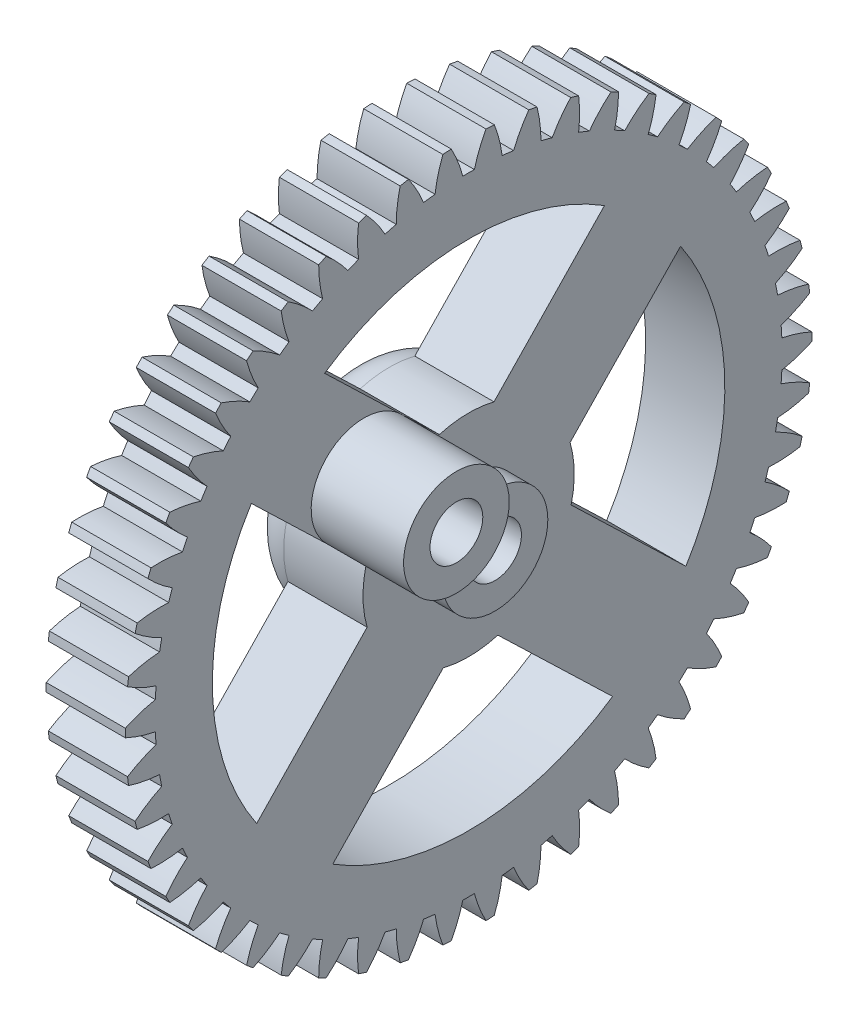
SolidWorks part; units mm, degrees
ref_plane "Plane1" through (0, 0, 0) normal (0, 0, 1) x (1, 0, 0)
ref_plane "Plane2" through (0, 0, 0) normal (0, 1, 0) x (1, 0, 0)
ref_plane "Plane3" through (0, 0, 0) normal (1, 0, 0) x (0, 0, -1)
other "Configuration Table"
sketch "HoldingSke" plane through (0, 0, 0) normal (0, 1, 0) x (1, 0, 0)
  line L0 (0, 0) -> (1.2856, -1.5321)
  line L1 (-15, 0) -> (100, 0) construction
  line L2 (0, 0) -> (-2.1039, 2.3779)
  line L3 (0, 0) -> (-11.863, 4.5341)
  line L4 (0, 0) -> (5.5511, 6.6156)
  line L5 (0, 0) -> (-46.8476, -17.4728)
  line L6 (0, 0) -> (-2.4869, -1.6779)
  line L7 (-2.1039, 2.3779) -> (8.6586, 51.2059)
  line L8 (-76.2, 54.61) -> (-75.9, 54.61)
  line L9 (-71.009, 38.7566) -> (-53.1078, 45.2721)
  line L10 (-76.2, 71.12) -> (104.1128, 71.12)
  line L11 (0, 0) -> (-3, 0)
  line L12 (-76.2, 101.6) -> (-76.181, 101.6)
  line L13 (24.9733, 27.94) -> (52.9518, 28.4284)
  line L14 (24.9733, 27.94) -> (24.9743, 27.94)
  line L15 (24.9733, 27.94) -> (100.4006, 29.5858)
  line L16 (-63.627, -0.5) -> (-12.827, -0.5)
  circle A0 centre (0, 0) radius 1
  circle A1 centre (0, 0) radius 11.874
  circle A2 centre (0, 0) radius 37.5
  circle A3 centre (0, 0) radius 1
  dimension "Num_teeth" = 50
  dimension "Pitch_radius" = 180.3128
  dimension "Width" = 3
  dimension "Thickness" = 3
sketch "BasProSke" plane through (0, 0, 0) normal (0, 1, 0) x (1, 0, 0)
  line L0 (-10, 0) -> (60, 0) construction
  line L1 (0, 0) -> (0, 13)
  line L2 (0, 0) -> (3, 0)
  line L3 (3, 0) -> (3, 13)
  line L4 (3, 13) -> (0, 13)
  dimension "Thickness" = 3
  dimension "Diameter" = 26
revolve "Base-Revolve" add sketch "BasProSke" angle 360 about L0
sketch "TooCutSke" plane through (0, 0, 0) normal (1, 0, 0) x (0, 0, -1)
  line L1 (0, 0) -> (0, 107) construction
  line L2 (0, 0) -> (-0.4259, 12.4927) construction
  line L3 (0, 0) -> (-1.5691, 24.9404) construction
  line L4 (-0.4259, 12.4927) -> (-0.7846, 12.4702) construction
  arc A0 (0.2187, 11.872) -> (-0.2187, 11.872) centre (0, 0) ccw
  arc A1 (0.6715, 13.0081) -> (-0.6715, 13.0081) centre (0, 0) ccw
  circle A2 centre (0, 0) radius 12.5 construction
  circle A3 centre (0, 0) radius 11.7462 construction
  arc A4 (-0.2187, 11.872) -> (-0.6715, 13.0081) centre (-5.0549, 10.6028) ccw
  arc A5 (0.6715, 13.0081) -> (0.2187, 11.872) centre (5.0549, 10.6028) ccw
extrude "ToothCut" cut sketch "TooCutSke" along normal through all
fillet "Breaks" [suppressed] radius 0.01 tangent propagation no
fillet "RootFillets" [suppressed] radius 0.126
pattern_circular "TeethCuts" count 50 every 7.2 about axis through (-10, 0, 0) along (1, 0, 0) of "ToothCut", "RootFillets", "Breaks"
sketch "HubNeaOneSke" plane through (0, 0, 0) normal (-1, 0, 0) x (0, 0, 1)
  circle A0 centre (0, 0) radius 11.874
  dimension "Diameter" = 23.748
extrude "HubNearOne" [suppressed] add sketch "HubNeaOneSke" along normal blind 47.0001
sketch "HubNeaBotSke" plane through (0, 0, 0) normal (-1, 0, 0) x (0, 0, 1)
  circle A0 centre (0, 0) radius 11.874
  dimension "Diameter" = 23.748
extrude "HubNearBoth" [suppressed] add sketch "HubNeaBotSke" along normal blind 23.5
ref_plane "FarPln" through (3, 0, 0) normal (1, 0, 0) x (0, 0, -1)
sketch "HubFarSke" plane through (3, 0, 0) normal (1, 0, 0) x (0, 0, -1)
  circle A0 centre (0, 0) radius 11.874
  dimension "Diameter" = 23.748
extrude "HubFar" [suppressed] add sketch "HubFarSke" along normal blind 23.5
sketch "BorSke" plane through (0, 0, 0) normal (1, 0, 0) x (0, 0, -1)
  circle A0 centre (0, 0) radius 1
  dimension "Diameter" = 2
extrude "Bore" cut sketch "BorSke" along normal mid plane 100.0001
sketch "KeySke" plane through (0, 0, 0) normal (1, 0, 0) x (0, 0, -1)
  line L0 (-0.4, 0) -> (-0.4, 1.3)
  line L1 (-0.4, 1.3) -> (0.4, 1.3)
  line L2 (0.4, 1.3) -> (0.4, 0)
  line L3 (0, 0) -> (0, 34) construction
  line L4 (-0.4, 0) -> (0.4, 0)
  dimension "Width" = 0.8
extrude "Keyway" [suppressed] cut sketch "KeySke" along normal mid plane 100.0001
pattern_circular "Keyway2" [suppressed] count 2 every 90 about axis through (-10, 0, 0) along (1, 0, 0)
sketch "草图1" plane through (3, 0, 0) normal (1, 0, 0) x (0, 0, -1)
  circle A0 centre (-3.9622, 3.8146) radius 1
  circle A1 centre (0, 0) radius 1 construction
  dimension "D1" = 5.5
extrude "切除-拉伸1" cut sketch "草图1" against normal blind 2
sketch "草图2" plane through (0, 0, 0) normal (-1, 0, 0) x (0, 0, 1)
  circle A0 centre (0, 0) radius 4
  circle A1 centre (0, 0) radius 1
extrude "凸台-拉伸1" add sketch "草图2" along normal blind 1.5
fillet "圆角1" radius 1.5 1 edges at (-1.5, 0, 4)
sketch "草图3" plane through (3, 0, 0) normal (1, 0, 0) x (0, 0, -1)
  circle A0 centre (-3.9622, 3.8146) radius 2
  circle A1 centre (-3.9622, 3.8146) radius 1
extrude "凸台-拉伸2" add sketch "草图3" along normal blind 3.5
sketch "草图5" plane through (3, 0, 0) normal (1, 0, 0) x (0, 0, -1)
  circle A0 centre (0, 0) radius 2
  circle A3 centre (0, 0) radius 1
extrude "凸台-拉伸3" add sketch "草图5" along normal blind 1
sketch "草图6" plane through (3, 0, 0) normal (1, 0, 0) x (0, 0, -1)
  line L0 (-5.4538, 8.0268) -> (-1.1084, 3.8434)
  line L1 (-8.2281, 5.1452) -> (-3.8827, 0.9617)
  line L2 (-8.0268, -5.4538) -> (-3.8434, -1.1084)
  line L3 (-5.1452, -8.2281) -> (-0.9617, -3.8827)
  line L4 (0.9617, 3.8827) -> (5.1452, 8.2281)
  line L5 (3.8827, -0.9617) -> (8.2281, -5.1452)
  line L6 (1.1084, -3.8434) -> (5.5529, -8.1222)
  line L7 (3.8434, 1.1084) -> (8.0268, 5.4538)
  arc A2 (-8.2281, 5.1452) -> (-8.0268, -5.4538) centre (0, 0) ccw
  circle A3 centre (-3.9622, 3.8146) radius 2 construction
  circle A4 centre (0, 0) radius 2 construction
  circle A5 centre (0, 0) radius 2 construction
  arc A6 (5.1452, 8.2281) -> (-5.4538, 8.0268) centre (0, 0) ccw
  arc A7 (-5.1452, -8.2281) -> (5.4538, -8.0268) centre (0, 0) ccw
  arc A8 (8.2281, -5.1452) -> (8.0268, 5.4538) centre (0, 0) ccw
  arc A9 (-3.8827, 0.9617) -> (-3.8434, -1.1084) centre (0, 0) ccw
  arc A10 (-0.9617, -3.8827) -> (1.1084, -3.8434) centre (0, 0) ccw
  arc A11 (3.8827, -0.9617) -> (3.8434, 1.1084) centre (0, 0) ccw
  arc A12 (0.9617, 3.8827) -> (-1.1084, 3.8434) centre (0, 0) ccw
extrude "切除-拉伸2" cut sketch "草图6" against normal blind 10 contours A11 L5 A8 L7 | A10 L3 A7 L6 | A9 L1 A2 L2 | A12 L4 A6 L0 region at (3, 7.1656, 0.1361) region at (3, -0.1361, 7.1656) region at (3, -7.1656, -0.1361) region at (3, 0.1361, -7.1656)
equation "' \"Module@HoldingSke\" = 6.35"
equation "' \"Num_teeth@HoldingSke\" = 12"
equation "' \"Ap@HoldingSke\" =  20"
equation "' \"Ap@HoldingSke\" = 20"
equation "' \"Width@HoldingSke\" = 0.5 * 25.4"
equation "' \"Hub_dia@HoldingSke\"= 1 * 25.4"
equation "' \"Hub_dia@HoldingSke\" = 1 * 25.4"
equation "' \"Overall_len@HoldingSke\" = 1.0 * 25.4"
equation "' \"Bore@HoldingSke\" = 0.75 * 25.4"
equation "' \"T_dim@HoldingSke\" = 0.1 * 25.4"
equation "' \"Width@KeySke\" = 0.25 * 25.4"
equation "' \"Show_teeth@HoldingSke\" = 13"
equation "' \"Backlash@HoldingSke\" = 0.009 * 25.4"
equation "' \"Addendum_fac@HoldingSke\" = 1.0"
equation "' \"Dedendum_fac@HoldingSke\" = 1.25"
equation "' \"Dedendum_add@HoldingSke\" = 0.00005 * 25.4"
equation "' \"Clearance_fac@HoldingSke\" = 0.25"
equation "\"Pitch@HoldingSke\" = 1 / \"Module@HoldingSke\""
equation "\"Overcut_dia@TooCutSke\" = (\"Num_teeth@HoldingSke\" + 2 * \"Addendum_fac@HoldingSke\") / \"Pitch@HoldingSke\" + 0.002 * 25.4"
equation "\"Pitch_dia@TooCutSke\" = \"Num_teeth@HoldingSke\" / \"Pitch@HoldingSke\""
equation "\"Base_dia@TooCutSke\" = \"Num_teeth@HoldingSke\" / \"Pitch@HoldingSke\" * cos((\"Ap@HoldingSke\"  * 3.14159265 / 180))"
equation "\"Root_dia@TooCutSke\" = (\"Num_teeth@HoldingSke\" + 2) / \"Pitch@HoldingSke\" - 2 * (\"Addendum_fac@HoldingSke\" + \"Dedendum_fac@HoldingSke\") / \"Pitch@HoldingSke\" - \"Dedendum_add@HoldingSke\" * 2"
equation "\"Half_ang@TooCutSke\" = 180 / \"Num_teeth@HoldingSke\""
equation "\"Half_CT@TooCutSke\" = \"Num_teeth@HoldingSke\" / \"Pitch@HoldingSke\" * sin((3.14159265 / 2 / \"Num_teeth@HoldingSke\")) / 2 - 7 * \"Backlash@HoldingSke\" / 4"
equation "\"Flank_rad@TooCutSke\" = \"Num_teeth@HoldingSke\" / \"Pitch@HoldingSke\" / 5"
equation "\"Radius@RootFillets\" = \"Clearance_fac@HoldingSke\" / \"Pitch@HoldingSke\" + \"Dedendum_add@HoldingSke\""
equation "\"Break_rad@Breaks\" = 0.02 / \"Pitch@HoldingSke\""
equation "\"Thickness@HoldingSke\" = \"Width@HoldingSke\""
equation "\"OAL@HoldingSke\" = \"Thickness@HoldingSke\""
equation "\"MHD@HoldingSke\" = (\"Num_teeth@HoldingSke\" + 2) / \"Pitch@HoldingSke\" - 2 * (\"Addendum_fac@HoldingSke\" + \"Dedendum_fac@HoldingSke\")  / \"Pitch@HoldingSke\" - \"Dedendum_add@HoldingSke\" * 2"
equation "\"MBD@HoldingSke\" = (\"Num_teeth@HoldingSke\" + 2) / \"Pitch@HoldingSke\" - 2 * (\"Addendum_fac@HoldingSke\" + \"Dedendum_fac@HoldingSke\")  / \"Pitch@HoldingSke\" - \"Dedendum_add@HoldingSke\" * 2 - 0.002 * 25.4"
equation "\"MHD@HoldingSke\" = ((sgn( \"MHD@HoldingSke\" - \"Hub_dia@HoldingSke\" )-1)*( \"MHD@HoldingSke\" - \"Hub_dia@HoldingSke\" ))/-2+ \"Hub_dia@HoldingSke\""
equation "\"MBD@HoldingSke\" = ((sgn( \"MBD@HoldingSke\" - \"Bore@HoldingSke\" )-1)*( \"MBD@HoldingSke\" - \"Bore@HoldingSke\" ))/-2+ \"Bore@HoldingSke\""
equation "\"OAL@HoldingSke\" = ((sgn( \"OAL@HoldingSke\" - \"Overall_len@HoldingSke\" )+1)*( \"OAL@HoldingSke\" - \"Overall_len@HoldingSke\" ))/2 + \"Overall_len@HoldingSke\" + 0.000002 * 25.4"
equation "\"Num_teeth@TeethCuts\" = int( \"Show_teeth@HoldingSke\" ) + 1"
equation "\"Num_teeth@TeethCuts\" = ((sgn( \"Num_teeth@TeethCuts\" - \"Num_teeth@HoldingSke\" )-1)*( \"Num_teeth@TeethCuts\" - \"Num_teeth@HoldingSke\" ))/-2+ \"Num_teeth@HoldingSke\""
equation "\"Num_teeth@TeethCuts\" = ((sgn( \"Num_teeth@TeethCuts\" - 2.0)+1)*( \"Num_teeth@TeethCuts\" - 2.0))/2 +2.0"
equation "\"Angle@TeethCuts\" = 360.0 / \"Num_teeth@HoldingSke\""
equation "\"Diameter@BasProSke\" = (\"Num_teeth@HoldingSke\" + 2 * \"Addendum_fac@HoldingSke\") / \"Pitch@HoldingSke\""
equation "\"Thickness@BasProSke\"  = \"Thickness@HoldingSke\""
equation "' \"Fillet_rad@BasProSke\" =  \"Thickness@HoldingSke\" * 0.05"
equation "' \"Fillet_rad@BasProSke\" = \"Thickness@HoldingSke\" * 0.05"
equation "\"MHD@HoldingSke\" = ((sgn( \"MHD@HoldingSke\" - \"Root_dia@TooCutSke\" )-1)*( \"MHD@HoldingSke\" - \"Root_dia@TooCutSke\" ))/-2+ \"Root_dia@TooCutSke\""
equation "\"Diameter@HubNeaOneSke\" = \"MHD@HoldingSke\""
equation "\"Length@HubNearOne\" = \"OAL@HoldingSke\" - \"Thickness@BasProSke\""
equation "\"Diameter@HubNeaBotSke\" = \"MHD@HoldingSke\""
equation "\"Length@HubNearBoth\" = ( \"OAL@HoldingSke\" - \"Thickness@BasProSke\" ) / 2.0"
equation "\"Thickness@FarPln\" = \"Thickness@BasProSke\""
equation "\"Diameter@HubFarSke\" = \"MHD@HoldingSke\""
equation "\"Length@HubFar\" = ( \"OAL@HoldingSke\" - \"Thickness@BasProSke\" ) / 2.0"
equation "\"Diameter@BorSke\" = \"MBD@HoldingSke\""
equation "\"D1@Bore\" = \"OAL@HoldingSke\" * 2.0"
equation "\"D1@Keyway\" = \"OAL@HoldingSke\" * 2.0"
equation "\"Offset@KeySke\" = \"T_dim@HoldingSke\" + \"MBD@HoldingSke\" / 2.0"
